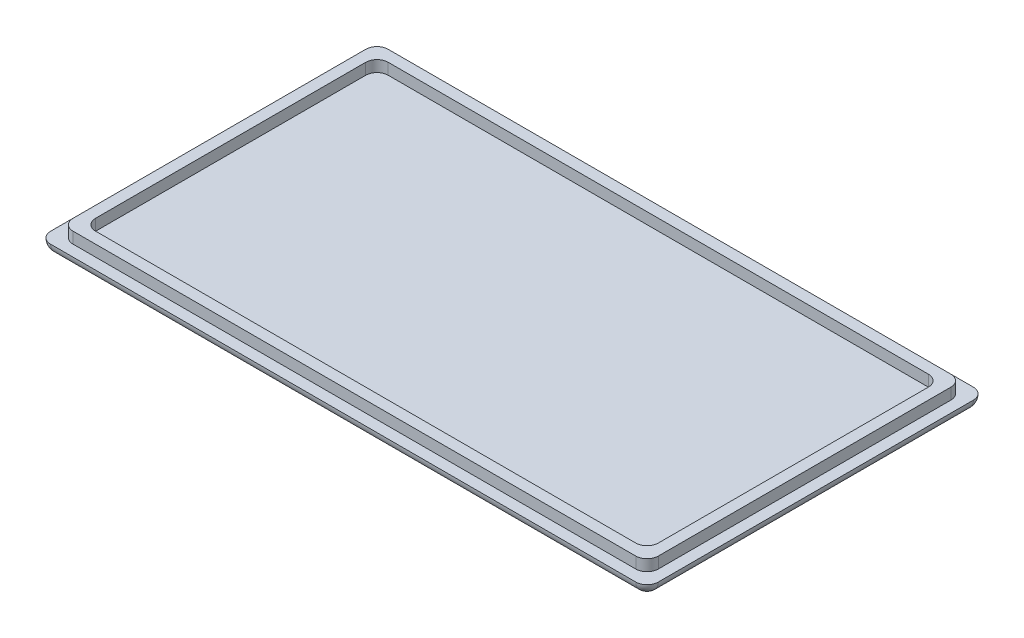
SolidWorks part; units mm, degrees
ref_plane "Front Plane" through (0, 0, 0) normal (0, 0, 1) x (1, 0, 0)
ref_plane "Top Plane" through (0, 0, 0) normal (0, 1, 0) x (1, 0, 0)
ref_plane "Right Plane" through (0, 0, 0) normal (1, 0, 0) x (0, 0, -1)
sketch "Sketch1" plane through (0, 0, 0) normal (0, 1, 0) x (1, 0, 0)
  line L1 (-135, -75) -> (135, -75)
  line L2 (-135, -75) -> (-135, 75)
  line L3 (-135, 75) -> (135, 75)
  line L4 (135, -75) -> (135, 75)
  line L5 (-135, -75) -> (135, 75) construction
  line L6 (-135, 75) -> (135, -75) construction
  point P0 (0, 0)
  dimension "D1" = 270
  dimension "D2" = 150
extrude "Boss-Extrude2" add sketch "Sketch1" along normal blind 5
sketch "Sketch4" plane through (0, 5, 0) normal (0, 1, 0) x (1, 0, 0)
  line L4 (-125, 65) -> (-125, -65)
  line L5 (-125, -65) -> (125, -65)
  line L6 (125, -65) -> (125, 65)
  line L7 (125, 65) -> (-125, 65)
  line L8 (130, -70) -> (130, 70)
  line L9 (130, 70) -> (-130, 70)
  line L10 (-130, 70) -> (-130, -70)
  line L11 (-130, -70) -> (130, -70)
  line L12 (130, -70) -> (130, 70)
  line L13 (130, 70) -> (-130, 70)
  line L14 (-130, 70) -> (-130, -70)
  line L15 (-130, -70) -> (130, -70)
  dimension "D1" = 5
  dimension "D2" = 5
extrude "Boss-Extrude3" add sketch "Sketch4" along normal blind 5
fillet "Fillet1" radius 5 16 edges at (135, 2.5, 75) (135, 2.5, -75) (-135, 2.5, -75) (-135, 2.5, 75) (-125, 7.5, 65) (-130, 7.5, 70) (130, 7.5, 70) (125, 7.5, 65) (130, 7.5, -70) (125, 7.5, -65) (-125, 7.5, -65) (-130, 7.5, -70) (0, 0, 75) (135, 0, 0) (0, 0, -75) (-135, 0, 0)
